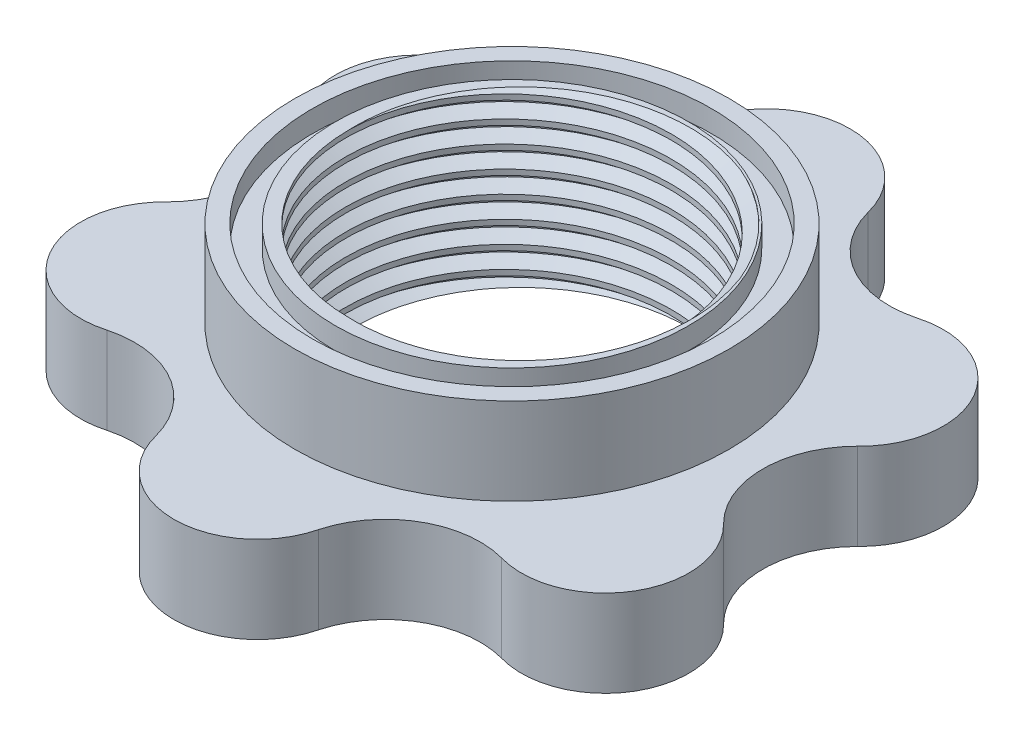
SolidWorks part; units mm, degrees
ref_plane "Alzado" through (0, 0, 0) normal (0, 0, 1) x (1, 0, 0)
ref_plane "Planta" through (0, 0, 0) normal (0, 1, 0) x (1, 0, 0)
ref_plane "Vista lateral" through (0, 0, 0) normal (1, 0, 0) x (0, 0, -1)
sketch "Croquis2" plane through (0, 0, 0) normal (0, 1, 0) x (1, 0, 0)
  line L0 (0.0018, 33.4846) -> (0.0018, -35.4698) construction
  line L5 (35.1399, -0.0013) -> (-31.8318, -0.0013) construction
  arc A1 (7.4858, 25.308) -> (-7.4822, 25.308) centre (0.0018, 23.4362) ccw
  arc A2 (25.6622, 6.1721) -> (18.1783, 19.1347) centre (20.2993, 11.7175) ccw
  arc A3 (18.1783, -19.1372) -> (25.6622, -6.1746) centre (20.2993, -11.72) ccw
  arc A4 (-7.4822, -25.3105) -> (7.4858, -25.3105) centre (0.0018, -23.4388) ccw
  arc A5 (-25.6587, -6.1746) -> (-18.1747, -19.1372) centre (-20.2957, -11.72) ccw
  arc A6 (-18.1091, 19.1156) -> (-25.6587, 6.1721) centre (-20.2957, 11.7175) ccw
  circle A7 centre (0.0018, -0.0013) radius 15
  arc A8 (-25.6587, 6.1721) -> (-25.6587, -6.1746) centre (-31.832, -0.0013) cw
  arc A9 (-7.4822, 25.308) -> (-18.1747, 19.1347) centre (-15.9151, 27.5676) cw
  arc A10 (18.1783, 19.1347) -> (7.4858, 25.308) centre (15.9187, 27.5676) cw
  arc A11 (25.6622, -6.1746) -> (25.6622, 6.1721) centre (31.8356, -0.0013) cw
  arc A12 (7.4858, -25.3105) -> (18.1783, -19.1372) centre (15.9187, -27.5701) cw
  arc A13 (-18.1747, -19.1372) -> (-7.4822, -25.3105) centre (-15.9151, -27.5701) cw
  point P2 (0, 0)
  point P15 (0.0018, -0.0013)
  point P33 (0.0018, -0.0013)
  point P35 (0, 0)
  dimension "D1" = 30
extrude "Saliente-Extruir2" add sketch "Croquis2" along normal blind 8 contours A5 A13 A4 A12 A3 A11 A2 A10 A1 A9 A6 A8 A7 region at (11.1345, 0, -19.2812)
sketch "Croquis3" plane through (0, 8, 0) normal (0, 1, 0) x (1, 0, 0)
  circle A0 centre (0, 0) radius 16.2742
  circle A1 centre (0.0018, -0.0013) radius 15 construction
  circle A2 centre (0.0018, -0.0013) radius 15
  point P2 (0, 0)
extrude "Saliente-Extruir3" add sketch "Croquis3" along normal blind 8
sketch "Croquis7" plane through (0, 8, 0) normal (0, 1, 0) x (1, 0, 0)
  circle A0 centre (0, 0) radius 20
  circle A1 centre (0, 0) radius 16.2742 construction
  circle A2 centre (0, 0) radius 16.2742
extrude "Saliente-Extruir8" add sketch "Croquis7" along normal blind 8 separate body
sketch "Croquis9" plane through (0, 16, 0) normal (0, 1, 0) x (1, 0, 0)
  circle A0 centre (0, 0) radius 18.3839
  circle A1 centre (0, 0) radius 16.2742 construction
  circle A2 centre (0, 0) radius 16.2742
extrude "Cortar-Extruir4" cut sketch "Croquis9" against normal blind 2
thread "Rosca2" pitch 2 method cut profile "Perfil de rosca2" start angle 0, offset 1, length 40, pitch 2, diameter 30
ref_plane "Plano2" through (15.0018, -1, 0.0013) normal (0, 0, 1) x (1, 0, 0)
sketch "Perfil de rosca2" plane through (15.0018, -1, 0.0013) normal (0, 0, 1) x (1, 0, 0)
  line L0 (0, 0) -> (0, 2) construction
  line L1 (0, 0) -> (1.0825, 0.625)
  line L2 (1.0825, 0.625) -> (1.0825, 0.875)
  line L3 (1.0825, 0.875) -> (0, 1.5)
  line L4 (1.0825, 0.75) -> (0, 0.75) construction
  line L11 (0, 0) -> (0, 1.5)
  point P2 (0, 0)
  dimension "Pitch" = 2
  dimension "Profile_Angle" = 60
  dimension "Profile_Land" = 0.25
  dimension "Profile_Height" = 1.0825
